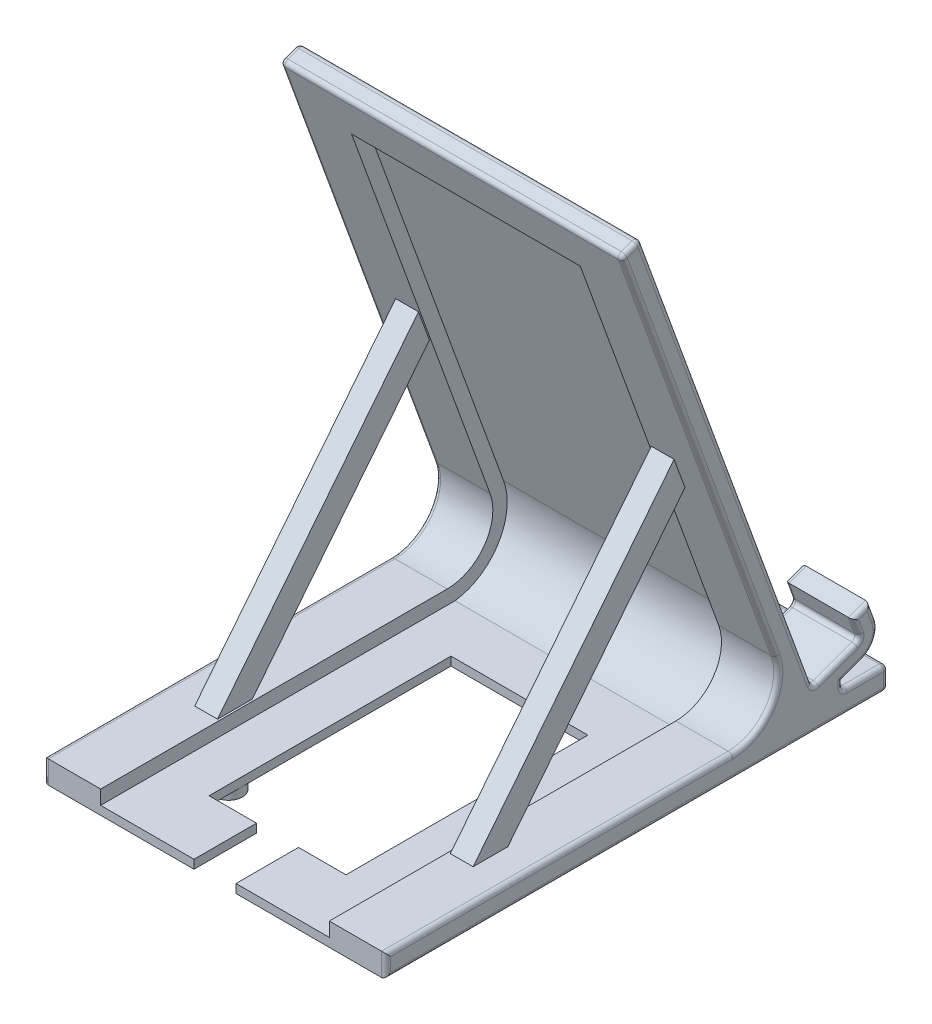
SolidWorks part; units mm, degrees
ref_plane "前视基准面" through (0, 0, 0) normal (0, 0, 1) x (1, 0, 0)
ref_plane "上视基准面" through (0, 0, 0) normal (0, 1, 0) x (1, 0, 0)
ref_plane "右视基准面" through (0, 0, 0) normal (1, 0, 0) x (0, 0, -1)
other "Configuration Table"
sketch "草图1" plane through (0, 0, 0) normal (0, 1, 0) x (1, 0, 0)
  line L1 (-37.5, -55) -> (37.5, -55)
  line L2 (-37.5, -55) -> (-37.5, 55)
  line L3 (-37.5, 55) -> (37.5, 55)
  line L4 (37.5, -55) -> (37.5, 55)
  line L5 (-37.5, -55) -> (37.5, 55) construction
  line L6 (-37.5, 55) -> (37.5, -55) construction
  point P0 (0, 0)
  dimension "D1" = 75
  dimension "D2" = 110
extrude "底座凸台-拉伸1" add sketch "草图1" along normal blind 5
sketch "草图2" plane through (-37.5, 0, 0) normal (-1, 0, 0) x (0, 0, 1)
  line L0 (-35.2112, 5) -> (3.4371, 111.1853)
  line L1 (55, 5) -> (-55, 5) construction
  line L2 (3.4371, 111.1853) -> (-0.7915, 112.7244)
  line L3 (-0.7915, 112.7244) -> (-40, 5)
  line L4 (-55, 5) -> (-55, 0) construction
  line L5 (-40, 5) -> (-35.2112, 5)
  dimension "D1" = 4.5
  dimension "D2" = 70
  dimension "D3" = 15
  dimension "D4" = 113
extrude "支架面板凸台-拉伸2" add sketch "草图2" against normal up to surface (75 mm away) up to face at (37.5, 2.5, 0)
sketch "草图4" plane through (37.5, 0, 0) normal (1, 0, 0) x (0, 0, -1)
  line L0 (45, 6.8199) -> (49.3969, 8.4202)
  line L1 (52.3853, 14.8288) -> (51.0172, 18.5875)
  line L2 (51.0172, 18.5875) -> (47.2584, 17.2195)
  line L3 (47.2584, 17.2195) -> (48.6265, 13.4607)
  line L4 (38.6319, 8.7588) -> (48.0288, 12.179)
  line L5 (40, 5) -> (0.7915, 112.7244) construction
  line L6 (38.6319, 8.7588) -> (40, 5)
  line L9 (45, 5) -> (40, 5)
  line L10 (45, 6.8199) -> (45, 5)
  arc A0 (49.3969, 8.4202) -> (52.3853, 14.8288) centre (47.6868, 13.1187) ccw
  arc A1 (48.0288, 12.179) -> (48.6265, 13.4607) centre (47.6868, 13.1187) ccw
  dimension "D6" = 1
  dimension "D1" = 90
  dimension "D2" = 90
  dimension "D3" = 10
  dimension "D4" = 4
  dimension "D5" = 4
  dimension "D7" = 5
  dimension "D8" = 4
extrude "支点凸台-拉伸4" add sketch "草图4" against normal blind 15
mirror "镜向1" about plane through (0, 0, 0) normal (1, 0, 0) of "支点凸台-拉伸4"
fillet "圆角1" radius 10 1 edges at (0, 5, -35.2112)
sketch "草图5" plane through (-37.5, 0, 0) normal (-1, 0, 0) x (0, 0, 1)
  line L0 (-17.4763, 53.7262) -> (-15.091, 60.2798)
  line L1 (-30.3266, 18.4202) -> (3.4371, 111.1853) construction
  line L2 (-15.091, 60.2798) -> (28.9432, 5)
  line L3 (-20.9297, 5) -> (55, 5) construction
  line L4 (28.9432, 5) -> (21.3375, 5)
  line L5 (21.3375, 5) -> (-17.4763, 53.7262)
extrude "凸台-拉伸1" add sketch "草图5" along normal blind 5 from offset 12 offset against normal yes
mirror "镜向2" about plane through (0, 0, 0) normal (1, 0, 0) of "凸台-拉伸1"
sketch "草图7" plane through (0, 0, 0) normal (1, 0, 0) x (0, 0, -1)
  line L0 (2.8962, 102.8486) -> (-0.0169, 101.7883)
  line L2 (-3.4371, 111.1853) -> (30.3088, 18.4692) construction
  line L4 (-0.524, 112.2455) -> (33.2792, 19.3718) construction
  line L6 (-55, 5) -> (20.7807, 5)
  line L7 (-55, 1.9) -> (22.6528, 1.9)
  line L8 (-55, 5) -> (20.9297, 5) construction
  line L18 (-55, 5) -> (-55, 0) construction
  line L19 (-3.4371, 111.1853) -> (30.3266, 18.4202) construction
  line L20 (0.7915, 112.7244) -> (-3.4371, 111.1853) construction
  line L21 (30.3088, 18.4692) -> (20.9297, 15)
  line L22 (20.9297, 15) -> (20.7807, 5)
  line L33 (-55, 5) -> (-55, 1.9)
  line L45 (-0.0169, 101.7883) -> (30.3088, 18.4692)
  line L46 (2.8962, 102.8486) -> (33.2792, 19.3718)
  arc A6 (20.9297, 5) -> (30.3266, 18.4202) centre (20.9297, 15) ccw construction
  arc A19 (21.1077, 1.9173) -> (33.2792, 19.3718) centre (19.6222, 15.9242) ccw construction
  arc A20 (20.7807, 5) -> (30.3088, 18.4692) centre (19.6222, 15.9242) ccw construction
  arc A21 (33.2792, 19.3718) -> (22.6528, 1.9) centre (20.9693, 14.8914) cw
  dimension "D3" = 10
  dimension "D4" = 13.1
  dimension "D1" = 3.1
  dimension "D2" = 3.1
extrude "切除-拉伸2" cut sketch "草图7" against normal mid plane 50.1
sketch "草图8" plane through (0, 0, 0) normal (0, -1, 0) x (1, 0, 0)
  line L0 (0, 0) -> (0, -42.2617) construction
  line L1 (-4.6, 53.3) -> (4.6, 53.3)
  line L2 (-15, 41.3) -> (-15, -11.7)
  line L3 (-15, -11.7) -> (15, -11.7)
  line L4 (15, 41.3) -> (15, -11.7)
  line L5 (-4.6, 53.3) -> (4.6, 53.3) construction
  line L6 (4.6, 53.3) -> (4.6, 41.3)
  line L7 (4.6, 41.3) -> (15, 41.3)
  line L8 (-4.6, 53.3) -> (-4.6, 41.3)
  line L9 (-4.6, 41.3) -> (-15, 41.3)
  line L11 (-4.5, 46.5) -> (-4.5, 54) construction
  dimension "D1" = 30
  dimension "D2" = 65
  dimension "D3" = 0.1
  dimension "D4" = 12
extrude "切除-拉伸3" cut sketch "草图8" against normal blind 2
fillet "手机支点圆角2" radius 1 62 edges at (22.5, 15.3401, -47.9425) (22.5, 12.696, -48.5931) (22.5, 16.7082, -51.7012) (22.5, 11.0056, -52.2184) (37.5, 16.7082, -51.7012) (37.5, 11.0056, -52.2184) (37.5, 15.3401, -47.9425) (37.5, 12.696, -48.5931) (22.5, 5.9099, -45) (37.5, 5.9099, -45) (37.5, 17.9035, -49.1378) (22.5, 17.9035, -49.1378) (22.5, 10.4689, -43.3304) (22.5, 7.62, -47.1985) (37.5, 7.62, -47.1985) (37.5, 10.4689, -43.3304) (-30, 8.7588, -38.6319) (-30, 5, -45) (30, 5, -45) (30, 8.7588, -38.6319) (0, 111.1853, 3.4371) (0, 112.7244, -0.7915) (0, 5, -55) (0, 0, -55) (37.5, 2.5, -55) (37.5, 0, 0) (37.5, 2.5, 55) (37.5, 5, 17.0351) (37.5, 64.8027, -13.4448) (37.5, 111.9548, 1.3228) (37.5, 60.7416, -19.7117) (37.5, 5, -50) (-37.5, 7.62, -47.1985) (-37.5, 11.0056, -52.2184) (-37.5, 16.7082, -51.7012) (-37.5, 17.9035, -49.1378) (-37.5, 15.3401, -47.9425) (-37.5, 12.696, -48.5931) (-37.5, 10.4689, -43.3304) (-37.5, 60.7416, -19.7117) (-37.5, 111.9548, 1.3228) (-37.5, 64.8027, -13.4448) (-37.5, 5, 17.0351) (-37.5, 2.5, 55) (-37.5, 0, 0) (-37.5, 2.5, -55) (-37.5, 5, -50) (-37.5, 5.9099, -45) (-22.5, 6.8794, -39.316) (-22.5, 10.4689, -43.3304) (-22.5, 12.696, -48.5931) (-22.5, 15.3401, -47.9425) (-22.5, 17.9035, -49.1378) (-22.5, 16.7082, -51.7012) (-22.5, 11.0056, -52.2184) (-22.5, 7.62, -47.1985) (-22.5, 5.9099, -45) (-22.5, 5, -42.5) (22.5, 6.8794, -39.316) (22.5, 5, -42.5) (37.5, 9.2642, -29.1212) (-37.5, 9.2642, -29.1212)
sketch "草图9" plane through (0, 0, 55) normal (0, 0, 1) x (1, 0, 0)
  line L1 (-4.6, 1.9) -> (4.6, 1.9)
  line L2 (-4.6, 1.9) -> (-4.6, 0)
  line L3 (-4.6, 0) -> (4.6, 0)
  line L4 (4.6, 1.9) -> (4.6, 0)
  line L5 (-36.5, 0) -> (36.5, 0) construction
  line L8 (4.6, 1.9) -> (4.6, 0) construction
  line L9 (-4.6, 1.9) -> (-4.6, 0) construction
  line L10 (-25.05, 1.9) -> (25.05, 1.9) construction
extrude "切除-拉伸4" cut sketch "草图9" against normal blind 5
sketch "草图10" plane through (0, 0, 0) normal (0, 1, 0) x (1, 0, 0)
  circle A0 centre (-18, -34) radius 1
  circle A1 centre (18, -34) radius 1
  circle A2 centre (18, 34) radius 1
  circle A3 centre (-18, 34) radius 1
  dimension "D1" = 2
  dimension "D2" = 2
  dimension "D3" = 2
  dimension "D4" = 2
extrude "拉伸-薄壁1" add sketch "草图10" against normal up to surface (2 mm away) thin thin type one direction wall 2
sketch "草图11" plane through (0, 0, 0) normal (0, 1, 0) x (1, 0, 0)
  line L0 (-18, -28) -> (-18, 28)
  line L1 (18, -28) -> (18, 28)
  circle A0 centre (-18, -34) radius 6 construction
  circle A1 centre (-18, 34) radius 6 construction
  circle A2 centre (18, -34) radius 6 construction
  circle A3 centre (18, 34) radius 6 construction
extrude "拉伸-薄壁2" add sketch "草图11" against normal up to surface (2.4 mm away) thin thin type mid plane wall 1
